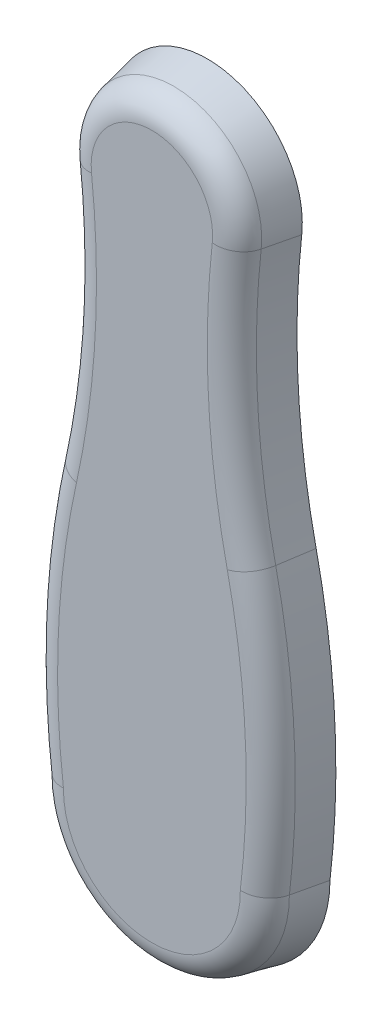
SolidWorks part; units mm, degrees
ref_plane "Front Plane" through (0, 0, 0) normal (0, 0, 1) x (1, 0, 0)
ref_plane "Top Plane" through (0, 0, 0) normal (0, 1, 0) x (1, 0, 0)
ref_plane "Right Plane" through (0, 0, 0) normal (1, 0, 0) x (0, 0, -1)
sketch "Sketch1" plane through (0, 0, 0) normal (0, 0, 1) x (1, 0, 0)
  line L0 (0, 200) -> (0, 0) construction
  arc A0 (-40, 0) -> (40, 0) centre (0, 0) ccw
  arc A1 (29.8258, 196.7715) -> (-29.8258, 196.7715) centre (0, 200) ccw
  arc A2 (-29.8258, 196.7715) -> (-35.0965, 100) centre (-328.0836, 164.4869) cw
  arc A3 (-35.0965, 100) -> (-40, 0) centre (257.8906, 35.5131) ccw
  arc A4 (29.8258, 196.7715) -> (35.0965, 100) centre (328.0836, 164.4869) ccw
  arc A5 (35.0965, 100) -> (40, 0) centre (-257.8906, 35.5131) cw
  dimension "D1" = 80
  dimension "D2" = 60
  dimension "D4" = 300
  dimension "D5" = 100
  dimension "D3" = 200
extrude "Boss-Extrude1" add sketch "Sketch1" along normal blind 20
draft "Draft2" type of draft neutral plane draft angle 12 faces to draft 4 face at (0, -20, 10) face at (-39.6488, 50.103, 10) face at (-30.4943, 148.2786, 10) face at (0, 213.3858, 10) neutral plane through (-35.0965, 100, 20) neutral plane normal (0, 0, 1) parameters "D1"=12
fillet "Fillet2" radius 10 6 edges at (41.7494, 50.206, 20) (28.5275, 148.1715, 20) (-41.7494, 50.206, 20) (-28.5275, 148.1715, 20) (0, -40, 20) (0, 230, 20)
shell "Shell1" [suppressed] thickness 3
ref_plane "Plane1" through (0, 0, 5) normal (0, 0, -1) x (-1, 0, 0)
sketch "Sketch3" plane through (-0.6767, -1.1425, 5) normal (0, 0, -1) x (0, 1, 0)
  line L0 (40.5922, 28.4467) -> (40.5922, -23.4754)
  line L1 (128.418, 17.3994) -> (128.418, -14.0853)
rib "Rib1" [suppressed] sketch "Sketch3" sketch "Sketch3" thickness 2 extrusion direction normal to sketch draft on yes draft angle 8 parameters "D1"=2, "D3"=8
sketch "Sketch5" [suppressed] plane through (0, 0, 5) normal (0, 0, -1) x (-1, 0, 0)
  circle A0 centre (0, 170) radius 5
  dimension "D1" = 10
  dimension "D2" = 30
sketch3d "3DSketch1" [suppressed]
  circle A0 centre (0, 170, 5) radius 5 construction
  point P0 (0, 170, 17)
  point P3 (0, 170, 0)
other "Mounting Boss1" [suppressed] parameters "BossHeight"=12, "BossDiam"=6, "StepHeight"=1, "StepDia"=5, "HoleDiam"=3.2, "CBoreDiam"=5, "CBoreDepth"=1.5, "D8"=0, "D9"=0, "D10"=0, "Clearance"=0.254, "FinLength"=8, "FinWidth"=1, "FinHeight"=8, "ChamferDist"=2.4, "BossDraft"=2, "HoleDraft"=1, "StepDraft"=0, "D19"=0, "FinDraft"=1, "ChamferAngle"=60
